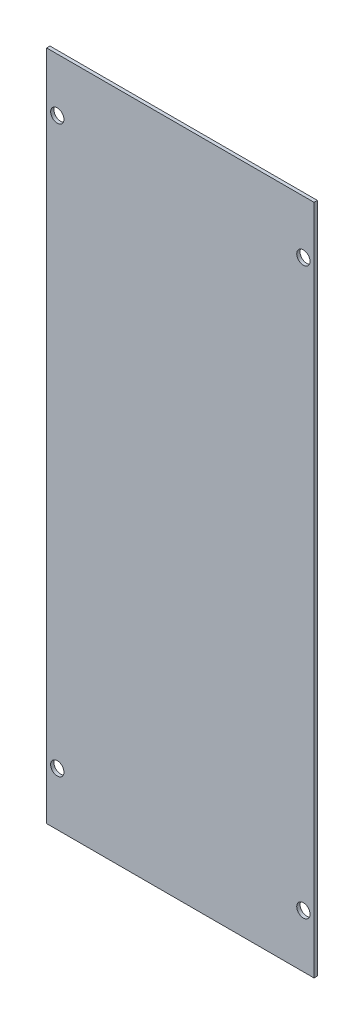
SolidWorks part; units mm, degrees
material "6061 Alloy"
ref_plane "Front" through (0, 0, 0) normal (0, 0, 1) x (1, 0, 0)
ref_plane "Top" through (0, 0, 0) normal (0, 1, 0) x (1, 0, 0)
ref_plane "Right" through (0, 0, 0) normal (1, 0, 0) x (0, 0, -1)
sketch "Sketch1" plane through (0, 0, 0) normal (0, 0, 1) x (1, 0, 0)
  line L1 (0, 0) -> (127.635, 0)
  line L2 (0, 0) -> (0, 320.675)
  line L3 (0, 320.675) -> (127.635, 320.675)
  line L4 (127.635, 0) -> (127.635, 320.675)
  dimension "D1" = 320.675
  dimension "D2" = 127.635
extrude "Boss-Extrude1" add sketch "Sketch1" along normal blind 1.5875
sketch "Sketch2" plane through (0, 0, 1.5875) normal (0, 0, 1) x (1, 0, 0)
  line L0 (0, 320.675) -> (0, 0) construction
  line L1 (127.635, 320.675) -> (0, 320.675) construction
  circle A0 centre (5.08, 295.275) radius 3.175
  dimension "D3" = 6.35
  dimension "D1" = 5.08
  dimension "D2" = 25.4
extrude "Cut-Extrude1" cut sketch "Sketch2" against normal blind 6.35
pattern_linear "LPattern1" count 2 spacing 117.475 along (1, 0, 0) count 2 spacing 269.875 along (0, -1, 0) of "Cut-Extrude1"
